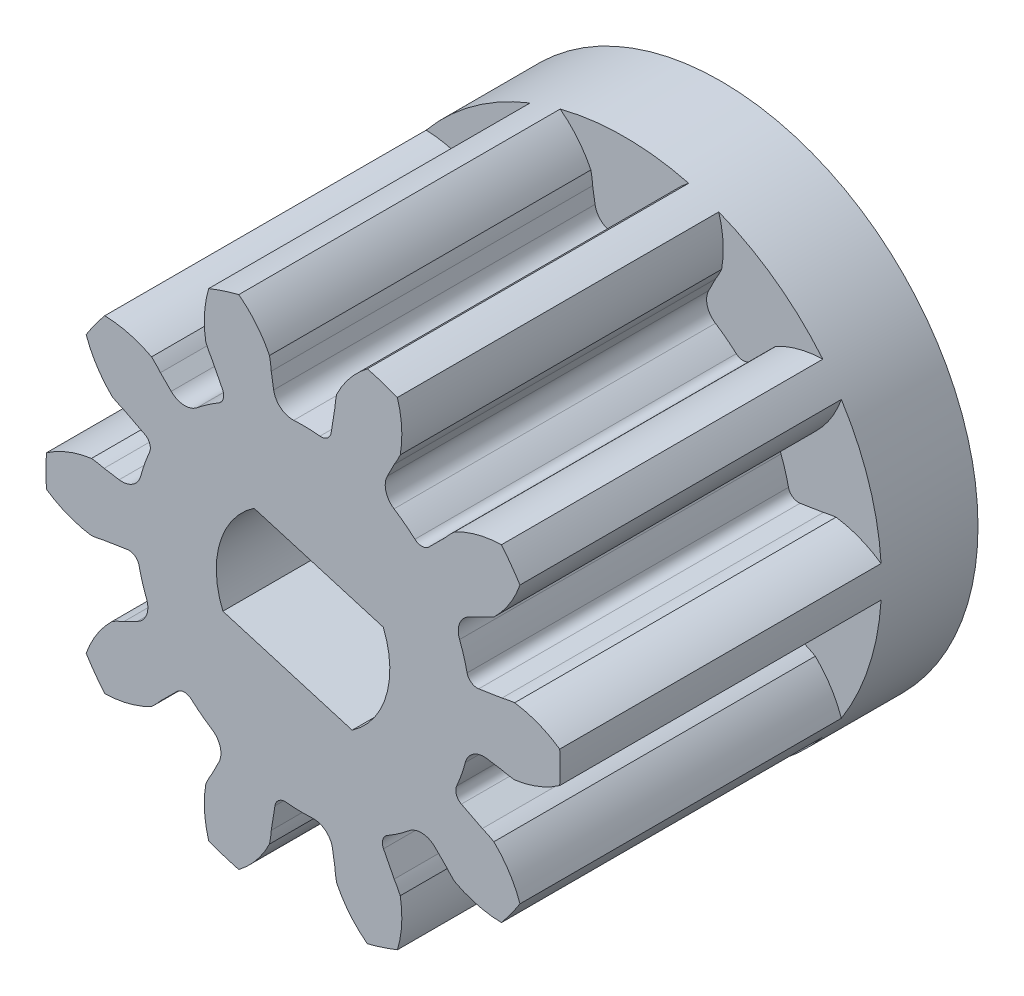
SolidWorks part; units mm, degrees
ref_plane "Plano frontal" through (0, 0, 0) normal (0, 0, 1) x (1, 0, 0)
ref_plane "Plano superior" through (0, 0, 0) normal (0, 1, 0) x (1, 0, 0)
ref_plane "Plano direito" through (0, 0, 0) normal (1, 0, 0) x (0, 0, -1)
sketch "Esboço1" plane through (0, 0, -62.4746) normal (0, 0, 1) x (1, 0, 0)
  line L6 (156.8392, -3.9468) -> (152.8174, -2.7533)
  line L7 (151.8501, -6.0128) -> (155.872, -7.2064)
  line L8 (156.8392, -3.9468) -> (152.8174, -2.7533)
  line L9 (151.8501, -6.0128) -> (155.872, -7.2064)
  circle A3 centre (154.3447, -4.9798) radius 8
  arc A8 (152.8174, -2.7533) -> (151.8501, -6.0128) centre (154.3447, -4.9798) ccw
  arc A9 (155.872, -7.2064) -> (156.8392, -3.9468) centre (154.3447, -4.9798) ccw
  arc A10 (152.8174, -2.7533) -> (151.8501, -6.0128) centre (154.3447, -4.9798) ccw
  arc A11 (155.872, -7.2064) -> (156.8392, -3.9468) centre (154.3447, -4.9798) ccw
  dimension "D2" = 0.2
  dimension "D1" = 16
extrude "Ressalto-extrusão1" add sketch "Esboço1" along normal up to surface (13 mm away) contours A3
sketch "Esboço4" plane through (0, 0, -49.4746) normal (0, 0, 1) x (1, 0, 0)
  line L0 (155.2598, -10.6986) -> (155.3347, -11.1661)
  line L1 (154.3447, -4.9798) -> (154.3447, -12.9798) construction
  line L2 (153.4703, -10.4436) -> (153.3547, -11.1661)
  line L3 (154.3447, -11.6448) -> (163.2458, -8.4137) construction
  circle A0 centre (154.3447, -4.9798) radius 5.2225 construction
  circle A1 centre (154.3447, -4.9798) radius 6.265 construction
  circle A2 centre (154.3447, -4.9798) radius 6.665 construction
  arc A3 (155.2598, -10.6986) -> (154.6341, -10.1943) centre (154.6674, -10.7934) ccw
  arc A4 (155.3347, -11.1661) -> (155.3897, -11.5624) centre (158.4742, -10.9324) ccw
  arc A5 (155.3897, -11.5624) -> (156.3447, -12.7258) centre (158.3126, -10.1367) ccw
  arc A6 (153.3547, -11.1661) -> (153.2997, -11.5624) centre (150.2152, -10.9324) cw
  arc A7 (153.2997, -11.5624) -> (152.3447, -12.7258) centre (150.3767, -10.1367) cw
  arc A8 (154.6341, -10.1943) -> (153.8185, -10.1758) centre (154.3447, -4.9798) cw
  arc A9 (156.3447, -12.7258) -> (152.3447, -12.7258) centre (154.3447, -4.9798) cw
  circle A10 centre (154.3447, -4.9798) radius 8 construction
  arc A11 (153.4703, -10.4436) -> (153.8185, -10.1758) centre (153.7863, -10.4941) cw
  point P17 (155.2973, -10.9324)
  point P31 (155.1699, -10.1367)
  point P34 (153.5194, -10.1367)
  dimension "D1" = 13.33
  dimension "D2" = 10.445
  dimension "D3" = 12.53
  dimension "D4" = 2.09
  dimension "D6" = 0.6
  dimension "D7" = 0.32
  dimension "D8" = 1.98
extrude "Corte-extrusão1" cut sketch "Esboço4" against normal blind 10
pattern_circular "PadrãoCircular1" count 10 over 360 about axis through (154.3447, -4.9798, 0) along (0, 0, 1) of "Corte-extrusão1"
sketch "Esboço5" plane through (0, 0, -62.4746) normal (0, 0, -1) x (-1, 0, 0)
  circle A2 centre (-154.3447, -4.9798) radius 2.75
  circle A3 centre (-154.3447, -4.9798) radius 2.75
  dimension "D1" = 0.2
extrude "Corte-extrusão2" cut sketch "Esboço5" against normal up to vertex (2.5 mm away)
fillet "Filete1" radius 1 1 edges at (151.5947, -4.9798, -59.9746)
